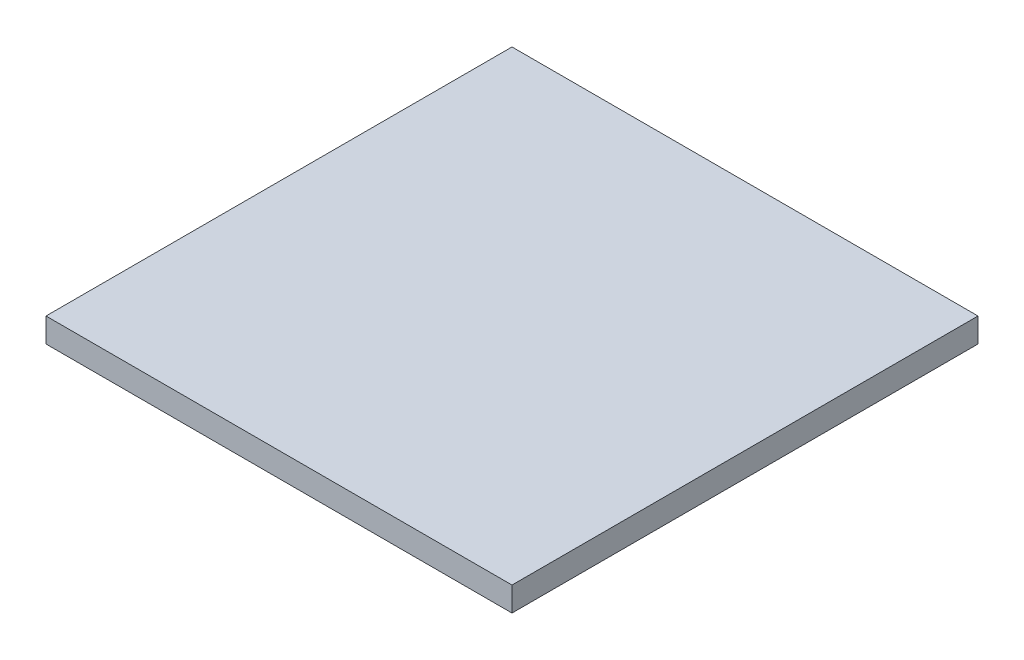
SolidWorks part; units mm, degrees
material "6061-T4 (SS)"
ref_plane "Front Plane" through (0, 0, 0) normal (0, 0, 1) x (1, 0, 0)
ref_plane "Top Plane" through (0, 0, 0) normal (0, 1, 0) x (1, 0, 0)
ref_plane "Right Plane" through (0, 0, 0) normal (1, 0, 0) x (0, 0, -1)
sketch "Sketch1" plane through (0, 0, 0) normal (0, 0, 1) x (1, 0, 0)
  line L1 (0, 0) -> (5, 0)
  line L2 (0, 0) -> (0, 5)
  line L3 (0, 5) -> (5, 5)
  line L4 (5, 0) -> (5, 5)
  dimension "D1" = 5
  dimension "D2" = 5
extrude "Boss-Extrude1" add sketch "Sketch1" along normal blind 96
sketch "Sketch2" plane through (0, 0, 0) normal (0, 1, 0) x (1, 0, 0)
  line L1 (0, 0) -> (96, 0)
  line L2 (0, 0) -> (0, -96)
  line L3 (0, -96) -> (96, -96)
  line L4 (96, 0) -> (96, -96)
  dimension "D1" = 96
  dimension "D2" = 96
extrude "Boss-Extrude2" add sketch "Sketch2" along normal blind 5
sketch "Sketch3" plane through (0, 0, 0) normal (0, -1, 0) x (1, 0, 0)
  line L0 (2.6746, 96) -> (2.6746, 0)
  line L1 (0, 96) -> (96, 96) construction
  line L2 (0, 0) -> (96, 0) construction
split line "Split Line1"
